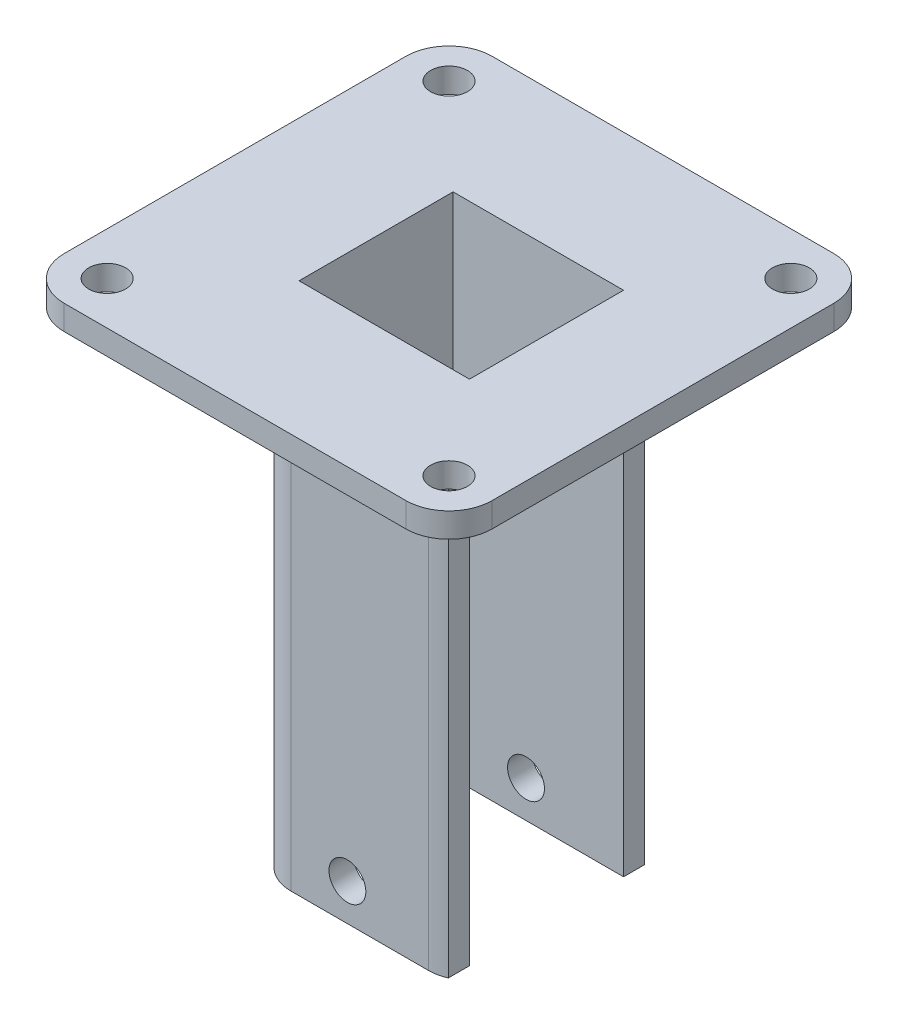
SolidWorks part; units mm, degrees
ref_plane "Front Plane" through (0, 0, 0) normal (0, 0, 1) x (1, 0, 0)
ref_plane "Top Plane" through (0, 0, 0) normal (0, 1, 0) x (1, 0, 0)
ref_plane "Right Plane" through (0, 0, 0) normal (1, 0, 0) x (0, 0, -1)
sketch "Sketch1" plane through (0, 0, 0) normal (0, 1, 0) x (1, 0, 0)
  line L0 (-57.93, -33) -> (48.39, -33)
  line L1 (-57.93, -33) -> (-57.93, 33)
  line L2 (48.39, -33) -> (48.39, 33)
  line L3 (-57.93, 33) -> (48.39, 33)
  line L6 (-6.4, 6.4) -> (6.4, 6.4)
  line L7 (-6.4, 6.4) -> (-6.4, -6.4)
  line L8 (6.4, 6.4) -> (6.4, -6.4)
  line L9 (-6.4, -6.4) -> (6.4, -6.4)
  point P1 (0, 0)
  dimension "D1" = 66
  dimension "D2" = 106.32
  dimension "D3" = 12.8
  dimension "D4" = 6.4
  dimension "D5" = 48.39
  dimension "D6" = 33
  dimension "D7" = 6.4
  dimension "D8" = 12.8
extrude "Boss-Extrude1" add sketch "Sketch1" along normal blind 3
sketch "Sketch2" plane through (0, 3, 0) normal (0, 1, 0) x (1, 0, 0)
  line L0 (-57.93, 33) -> (-57.93, -33) construction
  line L1 (48.39, 33) -> (-57.93, 33) construction
  line L2 (48.39, -33) -> (48.39, 33) construction
  line L3 (-57.93, -33) -> (48.39, -33) construction
  line L4 (-57.93, 33) -> (-57.93, 24)
  line L5 (48.39, 33) -> (39.39, 33)
  line L6 (48.39, -33) -> (48.39, -24)
  line L7 (-57.93, -33) -> (-48.93, -33)
  line L8 (-57.93, 24) -> (-48.93, 24)
  line L9 (-48.93, 24) -> (-48.93, 33)
  line L10 (39.39, 33) -> (39.39, 24)
  line L11 (39.39, 24) -> (48.39, 24)
  line L12 (-57.93, -24) -> (-48.93, -24)
  line L13 (-48.93, -24) -> (-48.93, -33)
  line L14 (-48.93, -33) -> (-48.93, -24)
  line L15 (39.39, -33) -> (39.39, -24)
  line L16 (39.39, -24) -> (48.39, -24)
  line L17 (-57.93, -24) -> (-57.93, -33)
  line L18 (-48.93, 33) -> (-57.93, 33)
  line L19 (39.39, -33) -> (48.39, -33)
  line L20 (48.39, 24) -> (48.39, 33)
  line M1 (-57.93, 33) -> (-57.93, -33)
  line M2 (-57.93, -33) -> (48.39, -33)
  line M3 (48.39, -33) -> (48.39, 33)
  line M4 (48.39, 33) -> (-57.93, 33)
  dimension "D1" = 9
  dimension "D2" = 9
  dimension "D3" = 9
  dimension "D4" = 9
  dimension "D5" = 9
  dimension "D6" = 9
  dimension "D7" = 9
  dimension "D8" = 9
extrude "Boss-Extrude2" [suppressed] add sketch "Sketch2" along normal blind 131 contours L8 L9 M4 M1 | L13 L12 M1 M2 | L16 L15 M2 M3 | L10 L11 M3 M4
sketch "Sketch3" plane through (0, 0, 0) normal (0, -1, 0) x (1, 0, 0)
  line L0 (-8.9, -9.4) -> (11.9, -9.4)
  line L1 (-8.9, -9.4) -> (-8.9, 9.4)
  line L2 (11.9, -9.4) -> (11.9, 9.4)
  line L3 (-8.9, 9.4) -> (11.9, 9.4)
  line L4 (-11.9, 12.4) -> (14.9, 12.4)
  line L5 (14.9, -12.4) -> (14.9, 12.4)
  line L6 (-11.9, -12.4) -> (14.9, -12.4)
  line L7 (-11.9, -12.4) -> (-11.9, 12.4)
  dimension "D1" = 8.9
  dimension "D2" = 20.8
  dimension "D3" = 18.8
  dimension "D4" = 9.4
  dimension "D5" = 3
extrude "Boss-Extrude3" add sketch "Sketch3" along normal blind 62
sketch "Sketch4" plane through (0, 0, -12.4) normal (0, 0, -1) x (-1, 0, 0)
  line L1 (11.9, 0) -> (-14.9, 0) construction
  circle A0 centre (0, -57.5) radius 2.25
  dimension "D1" = 57.5
  dimension "D2" = 4.5
extrude "Cut-Extrude3" cut sketch "Sketch4" against normal through all
fillet "Fillet1" [suppressed] radius 5
fillet "Fillet2" radius 5 4 edges at (-11.9, -31, 12.4) (14.9, -31, -12.4) (14.9, -31, 12.4) (-11.9, -31, -12.4)
sketch "Sketch6" [suppressed] plane through (0, 134, 0) normal (0, 1, 0) x (1, 0, 0)
  line L1 (-57.93, 33) -> (48.39, 33)
  line L2 (-57.93, 33) -> (-57.93, -33)
  line L3 (-57.93, -33) -> (48.39, -33)
  line L4 (48.39, 33) -> (48.39, -33)
extrude "Boss-Extrude4" [suppressed] add sketch "Sketch6" along normal blind 3
sketch "Sketch41" plane through (0, 0, 0) normal (0, -1, 0) x (1, 0, 0)
  line L0 (48.39, 33) -> (48.39, -33) construction
  line L1 (48.39, -33) -> (-57.93, -33) construction
  line L2 (-57.93, -33) -> (-57.93, 33) construction
  line L3 (-57.93, 33) -> (48.39, 33) construction
  line L4 (-6.9, -12.4) -> (9.9, -12.4)
  line L5 (-11.9, 7.4) -> (-11.9, -7.4)
  line L6 (9.9, 12.4) -> (-6.9, 12.4)
  line L7 (14.9, -7.4) -> (14.9, 7.4)
  line L8 (-6.9, -12.4) -> (9.9, -12.4)
  line L9 (-11.9, 7.4) -> (-11.9, -7.4)
  line L10 (9.9, 12.4) -> (-6.9, 12.4)
  line L11 (14.9, -7.4) -> (14.9, 7.4)
  line L12 (-6.9, -12.4) -> (9.9, -12.4) construction
  line L13 (48.39, 33) -> (48.39, -33)
  line L14 (48.39, -33) -> (-57.93, -33)
  line L15 (-57.93, -33) -> (-57.93, 33)
  line L16 (-57.93, 33) -> (48.39, 33)
  line L17 (-6.9, -12.4) -> (9.9, -12.4)
  arc A0 (-11.9, -7.4) -> (-6.9, -12.4) centre (-6.9, -7.4) ccw construction
  arc A1 (-11.9, -7.4) -> (-6.9, -12.4) centre (-6.9, -7.4) ccw
  arc A4 (-11.9, -7.4) -> (-6.9, -12.4) centre (-6.9, -7.4) ccw
  arc A5 (-6.9, 12.4) -> (-11.9, 7.4) centre (-6.9, 7.4) ccw
  arc A6 (14.9, 7.4) -> (9.9, 12.4) centre (9.9, 7.4) ccw
  arc A7 (9.9, -12.4) -> (14.9, -7.4) centre (9.9, -7.4) ccw
  arc A8 (-11.9, -7.4) -> (-6.9, -12.4) centre (-6.9, -7.4) ccw
  arc A9 (-6.9, 12.4) -> (-11.9, 7.4) centre (-6.9, 7.4) ccw
  arc A10 (14.9, 7.4) -> (9.9, 12.4) centre (9.9, 7.4) ccw
  arc A11 (9.9, -12.4) -> (14.9, -7.4) centre (9.9, -7.4) ccw
  line M9 (-57.93, 33) -> (-57.93, -33)
  line M10 (-57.93, -33) -> (48.39, -33)
  line M11 (48.39, -33) -> (48.39, 33)
  line M12 (48.39, 33) -> (-57.93, 33)
  line M13 (9.9, -12.4) -> (-6.9, -12.4)
  arc M14 (-6.9, -12.4) -> (-11.9, -7.4) centre (-6.9, -7.4) cw
  line M15 (-11.9, -7.4) -> (-11.9, 7.4)
  arc M16 (-11.9, 7.4) -> (-6.9, 12.4) centre (-6.9, 7.4) cw
  line M17 (-6.9, 12.4) -> (9.9, 12.4)
  arc M18 (9.9, 12.4) -> (14.9, 7.4) centre (9.9, 7.4) cw
  line M19 (14.9, 7.4) -> (14.9, -7.4)
  arc M20 (14.9, -7.4) -> (9.9, -12.4) centre (9.9, -7.4) cw
  dimension "D1" = 0
extrude "Boss-Extrude16" add sketch "Sketch41" along normal blind 3 contours M12 M9 M10 M11 M20 M13 M14 M15 M16 M17 M18 M19 region at (47.1386, 0, 0)
sketch "Sketch45" plane through (0, 3, 0) normal (0, 1, 0) x (1, 0, 0)
  line L4 (-57.93, 33) -> (-57.93, -33)
  line L5 (-57.93, -33) -> (48.39, -33)
  line L6 (48.39, -33) -> (48.39, 33)
  line L7 (48.39, 33) -> (-57.93, 33)
  line L8 (-57.93, 33) -> (-57.93, -33)
  line L9 (-57.93, -33) -> (48.39, -33)
  line L10 (48.39, -33) -> (48.39, 33)
  line L11 (48.39, 33) -> (-57.93, 33)
  dimension "D1" = 0
extrude "Cut-Extrude22" cut sketch "Sketch45" against normal blind 3
sketch "Sketch46" plane through (0, -3, 0) normal (0, -1, 0) x (1, 0, 0)
  line L0 (11.9, -9.4) -> (11.9, 9.4) construction
  line L1 (14.9, -7.4) -> (14.9, 7.4) construction
  line L2 (-6.9, -12.4) -> (9.9, -12.4) construction
  line L3 (9.9, 12.4) -> (-6.9, 12.4) construction
  line L4 (11.9, -12.4) -> (11.9, 12.4)
  line L5 (14.9, -12.4) -> (14.9, 12.4)
  line L6 (11.9, -12.4) -> (14.9, -12.4)
  line L7 (14.9, 12.4) -> (11.9, 12.4)
extrude "Cut-Extrude23" cut sketch "Sketch46" along normal through all
sketch "Sketch47" plane through (0, -3, 0) normal (0, -1, 0) x (-1, 0, 0)
  line L0 (-27.94, 0) -> (27.94, 0) construction
  line L1 (0, 27.94) -> (0, -27.94) construction
  line L2 (0, 0) -> (-8.6492, 0) construction
  line L3 (0, 0) -> (0, -4.5998) construction
  circle A0 centre (20.86, -20.86) radius 2.25
  circle A1 centre (20.86, 20.86) radius 2.25
  circle A2 centre (-20.86, -20.86) radius 2.25
  circle A3 centre (-20.86, 20.86) radius 2.25
  dimension "D1" = 4.5
  dimension "D2" = 20.86
  dimension "D3" = 20.86
extrude "Cut-Extrude25" cut sketch "Sketch47" against normal through all
sketch "Sketch49" plane through (0, -3, 0) normal (0, -1, 0) x (1, 0, 0)
  line L0 (-20.86, -26.11) -> (20.86, -26.11)
  line L1 (-26.11, -20.86) -> (-26.11, 20.86)
  line L2 (-20.86, 26.11) -> (20.86, 26.11)
  line L3 (26.11, -20.86) -> (26.11, 20.86)
  line L4 (-57.93, -33) -> (48.39, -33) construction
  line L5 (48.39, -33) -> (48.39, 33) construction
  line L6 (48.39, 33) -> (-57.93, 33) construction
  line L7 (-57.93, 33) -> (-57.93, -33) construction
  line L8 (-57.93, -33) -> (48.39, -33)
  line L9 (48.39, -33) -> (48.39, 33)
  line L10 (48.39, 33) -> (-57.93, 33)
  line L11 (-57.93, 33) -> (-57.93, -33)
  circle A24 centre (-20.86, -20.86) radius 5.25
  arc A25 (-26.11, -20.86) -> (-20.86, -26.11) centre (-20.86, -20.86) ccw
  circle A27 centre (20.86, -20.86) radius 5.25
  arc A28 (20.86, -26.11) -> (26.11, -20.86) centre (20.86, -20.86) ccw
  circle A30 centre (-20.86, 20.86) radius 5.25
  arc A31 (-20.86, 26.11) -> (-26.11, 20.86) centre (-20.86, 20.86) ccw
  circle A33 centre (20.86, 20.86) radius 5.25
  arc A34 (26.11, 20.86) -> (20.86, 26.11) centre (20.86, 20.86) ccw
  dimension "D1" = 3
  dimension "D2" = 3
  dimension "D3" = 3
  dimension "D4" = 3
extrude "Cut-Extrude26" cut sketch "Sketch49" against normal through all
fillet "Fillet9" radius 5 9 edges at (10.9215, -3, -12.2945) (1.5, -3, -12.4) (-10.4355, -3, -10.9355) (-11.9, -3, 0) (-10.4355, -3, 10.9355) (10.9215, -3, 12.2945) (11.9, -3, 10.6913) (11.9, -3, -10.6913) (1.5, -3, 12.4)
sketch "Sketch50" plane through (11.9, 0, 0) normal (-1, 0, 0) x (0, 0, 1)
  line L4 (-9.4, -3) -> (9.4, -3)
  line L5 (9.4, -3) -> (9.4, 0)
  line L6 (9.4, 0) -> (-9.4, 0)
  line L7 (-9.4, 0) -> (-9.4, -3)
  line L8 (-9.4, -3) -> (9.4, -3)
  line L9 (9.4, -3) -> (9.4, 0)
  line L10 (9.4, 0) -> (-9.4, 0)
  line L11 (-9.4, 0) -> (-9.4, -3)
  dimension "D1" = 0
extrude "Boss-Extrude17" [suppressed] add sketch "Sketch50" along normal blind 5.5
sketch "Sketch7" [suppressed] plane through (0, 137, 0) normal (0, 1, 0) x (1, 0, 0)
  line L0 (-48.93, -33) -> (39.39, -33) construction
  line L1 (48.39, -33) -> (48.39, 33) construction
  circle A0 centre (0, 0) radius 26.5
  dimension "D1" = 48.39
  dimension "D2" = 53
  dimension "D3" = 33
extrude "Cut-Extrude4" [suppressed] cut sketch "Sketch7" against normal blind 5
sketch "Sketch8" [suppressed] plane through (0, 134, 0) normal (0, -1, 0) x (1, 0, 0)
  line L0 (48.39, -24) -> (45.39, -24)
  line L1 (48.39, -24) -> (48.39, 24)
  line L2 (45.39, -24) -> (45.39, 24)
  line L3 (48.39, 24) -> (45.39, 24)
  line L4 (39.39, 24) -> (48.39, 24) construction
  dimension "D1" = 3
extrude "Boss-Extrude5" [suppressed] add sketch "Sketch8" along normal blind 131
sketch "Sketch10" [suppressed] plane through (0, 134, 0) normal (0, -1, 0) x (1, 0, 0)
  line L4 (0, 0) -> (14.8362, 0) construction
  circle A0 centre (25.3422, 22.8387) radius 1.625
  circle A1 centre (25.3422, -22.8387) radius 1.625
  circle A3 centre (0, 0) radius 26.5 construction
  circle A4 centre (0, 0) radius 26.5
  dimension "D4" = 3.25
  dimension "D5" = 34.115
extrude "Cut-Extrude6" [suppressed] cut sketch "Sketch10" against normal through all contours A0 | A1
sketch "Sketch21" [suppressed] plane through (0, 134, 0) normal (0, -1, 0) x (1, 0, 0)
  circle A0 centre (-33.93, 5.05) radius 1.625
  circle A1 centre (0, 0) radius 26.5 construction
  circle A2 centre (0, 0) radius 26.5
  dimension "D1" = 33.93
  dimension "D3" = 3.25
  dimension "D2" = 5.05
extrude "Cut-Extrude12" [suppressed] cut sketch "Sketch21" against normal up to next contours A0
sketch "Sketch11" [suppressed] plane through (0, 134, 0) normal (0, -1, 0) x (1, 0, 0)
  line L0 (-66, 44) -> (-47.7966, 14.3367) construction
  line L1 (-37.8467, 24.3295) -> (-35.4201, 26.404)
  line L2 (-45.5, 30) -> (-48.93, 47)
  line L5 (-45.5, 33) -> (-48.93, 33)
  line L8 (-48.93, 24) -> (-48.93, 33) construction
  line L9 (-48.93, 47) -> (-48.93, 33)
  line L11 (-45.7507, 11.0029) -> (-47.7966, 14.3367)
  line L12 (-51.4178, 12.7275) -> (-48.9912, 14.802)
  arc A3 (-37.8467, 24.3295) -> (-45.5, 30) centre (-45.5, 22) ccw
  arc A6 (-35.4201, 26.404) -> (-45.5, 33) centre (-45.5, 22) ccw
  arc A7 (-47.7966, 14.3367) -> (-48.9912, 14.802) centre (-45.5, 22) ccw
  circle A8 centre (-45.5, 22) radius 11 construction
  circle A9 centre (-45.5, 22) radius 8 construction
  arc A10 (-45.7507, 11.0029) -> (-51.4178, 12.7275) centre (-45.5, 22) ccw
  point P3 (-45.5, 22)
  point P4 (-23.505, 28.7245)
  point P5 (-23.505, 28.7245)
  point P8 (-27, 50)
  point P11 (-27, 45)
  point P16 (-17.5, 22)
  point P25 (-17.5, 22)
  dimension "D1" = 3
extrude "Boss-Extrude6" [suppressed] add sketch "Sketch11" along normal blind 12.2
sketch "Sketch12" [suppressed] plane through (0, 121.8, 0) normal (0, -1, 0) x (1, 0, 0)
  line L0 (-36.5645, -4.536) -> (-34.8232, -0.6054) construction
  line L1 (-45.5, 50) -> (-60, 50) construction
  line L2 (-36.5645, -4.536) -> (-19.842, 33.2102)
  line L3 (-45.5, 50) -> (-60, 50)
  line L5 (-60, 50) -> (-60, 47) construction
  line L6 (-60, 50) -> (-60, 44)
  line L7 (-66, 44) -> (-60, 44) construction
  line L8 (-47.3545, -2.9311) -> (-46.1381, -5.9927) construction
  line L10 (-66, 44) -> (-60, 44)
  line L11 (-66, 44) -> (-46.1381, -5.9927)
  arc A0 (-46.1381, -5.9927) -> (-36.5645, -4.536) centre (-45.5, 22) ccw construction
  arc A1 (-19.842, 33.2102) -> (-45.5, 50) centre (-45.5, 22) ccw construction
  arc A2 (-46.1381, -5.9927) -> (-36.5645, -4.536) centre (-45.5, 22) ccw
  arc A3 (-19.842, 33.2102) -> (-45.5, 50) centre (-45.5, 22) ccw
  point P9 (-56, 25.1613)
  point P12 (-61, 50)
  point P13 (-61, 25.1613)
  point P15 (-61, 35)
  point P16 (-56, 35)
extrude "Boss-Extrude7" [suppressed] add sketch "Sketch12" along normal blind 5
sketch "Sketch13" [suppressed] plane through (0, 116.8, 0) normal (0, -1, 0) x (1, 0, 0)
  line L2 (-66, 44) -> (-46.1381, -5.9927) construction
  line L3 (-59.8699, 28.5705) -> (-53.0906, 11.5068)
  arc A2 (-53.0906, 11.5068) -> (-59.8699, 28.5705) centre (-49.8906, 22.6567) ccw
  dimension "D1" = 23.2
extrude "Cut-Extrude7" [suppressed] cut sketch "Sketch13" against normal blind 2
sketch "Sketch14" [suppressed] plane through (0, 116.8, 0) normal (0, -1, 0) x (1, 0, 0)
  line L0 (-62.8216, 36) -> (-31.5, 36)
  line L1 (-45.5, 50) -> (-60, 50) construction
  line L2 (-66, 44) -> (-59.8699, 28.5705) construction
  line L3 (-66, 44) -> (-62.8216, 36)
  line L4 (-59.8164, 36) -> (-31.5, 36) construction
  line L5 (-60.7854, 39) -> (-62.7719, 44)
  line L6 (-31.5, 8) -> (-31.5, 36)
  line L7 (-66, -44) -> (-66, 44) construction
  line L8 (-36.5645, -4.536) -> (-19.842, 33.2102) construction
  line L9 (-53.0906, 11.5068) -> (-46.1381, -5.9927) construction
  line L10 (-28.5, 13.6674) -> (-28.5, 39)
  line L11 (-60.7854, 39) -> (-28.5, 39)
  line L12 (-59.8164, 39) -> (-28.5, 39) construction
  line L13 (-28.5, 6.8958) -> (-28.5, 39) construction
  line L14 (-31.5, 8) -> (-51.6974, 8)
  line L15 (-51.6974, 8) -> (-50.5055, 5)
  line L17 (-32.3399, 5) -> (-28.5, 13.6674)
  line L18 (-31.0108, 8) -> (-50.9566, 8) construction
  line L19 (-32.3399, 5) -> (-50.5055, 5)
  line L20 (-31.5, 6.8958) -> (-28.5, 13.6674)
  line L21 (-31.0108, 5) -> (-50.9566, 5) construction
  line L22 (-31.5, 6.8958) -> (-31.5, 36) construction
  line L23 (-60, 44) -> (-66, 44) construction
  line L24 (-62.7719, 44) -> (-66, 44)
  point P16 (-59, 42)
  point P17 (-56, 40)
  dimension "D1" = 14
  dimension "D2" = 34.5
  dimension "D3" = 3
  dimension "D4" = 42
  dimension "D6" = 3
  dimension "D5" = 3
extrude "Boss-Extrude8" [suppressed] add sketch "Sketch14" along normal blind 24
sketch "Sketch29" [suppressed] plane through (0, 134, 0) normal (0, -1, 0) x (1, 0, 0)
  line L1 (-57.93, -24) -> (-57.93, 24) construction
  line L4 (-48.93, 24) -> (-48.93, 27)
  line L5 (-48.93, 24) -> (-48.93, 33) construction
  line L6 (-57.93, 2) -> (-41.93, 2)
  line L7 (-57.93, 5) -> (-41.93, 5)
  line L8 (-48.93, 24) -> (-41.93, 24)
  line L9 (-48.93, 27) -> (-41.93, 27)
  line L14 (-57.93, 2) -> (-57.93, 5)
  arc A0 (-41.93, 2) -> (-41.93, 27) centre (-41.93, 14.5) ccw
  arc A1 (-41.93, 5) -> (-41.93, 24) centre (-41.93, 14.5) ccw
  circle A3 centre (-41.93, 14.5) radius 12.5 construction
  circle A4 centre (-41.93, 14.5) radius 9.5 construction
  point P1 (-32.2829, 11.5)
  point P15 (-29.8291, 15.1546)
  dimension "D1" = 25
  dimension "D3" = 3
  dimension "D4" = 16
extrude "Boss-Extrude12" [suppressed] add sketch "Sketch29" along normal blind 11.3 contours L14 L7 A1 L8 L4 L9 A0 L6
sketch "Sketch25" [suppressed] plane through (0, 122.7, 0) normal (0, -1, 0) x (1, 0, 0)
  line L2 (-57.93, 24) -> (-41.93, 24) construction
  line L3 (-57.93, 5) -> (-57.93, 24) construction
  line L4 (-57.93, 5) -> (-57.93, 24)
  line L6 (-57.93, 5) -> (-41.93, 5) construction
  line L7 (-57.93, 24) -> (-41.93, 24)
  line L8 (-57.93, 5) -> (-41.93, 5)
  arc A0 (-41.93, 5) -> (-41.93, 24) centre (-41.93, 14.5) ccw construction
  arc A1 (-41.93, 5) -> (-41.93, 24) centre (-41.93, 14.5) ccw
  circle A2 centre (-41.93, 14.5) radius 3.9
  point P13 (-42.4424, 11.9931)
  point P14 (-32.8261, 23.4534)
  point P15 (-48.4176, 17.0069)
  point P16 (-38.8013, 28.4671)
  dimension "D1" = 7.8
extrude "Boss-Extrude11" [suppressed] add sketch "Sketch25" against normal blind 3
sketch "Sketch32" [suppressed] plane through (0, 137, 0) normal (0, 1, 0) x (1, 0, 0)
  line L6 (-42.2096, -2.5625) -> (-42.2096, 0.578) construction
  line L7 (-48.5223, 1) -> (-45.43, 1) construction
  line L8 (-48.5223, -2) -> (-48.5223, 1) construction
  line L9 (-42.2096, -20.4375) -> (-42.2096, -23.578) construction
  line L10 (-48.5223, -24) -> (-45.43, -24) construction
  line L11 (-48.5223, -21) -> (-48.5223, -24) construction
  line L13 (-42.2096, -2.5625) -> (-42.2096, 0.578)
  line L14 (-48.5223, 1) -> (-45.43, 1)
  line L15 (-48.5223, -2) -> (-48.5223, 1)
  line L16 (-42.2096, -20.4375) -> (-42.2096, -23.578)
  line L17 (-48.5223, -24) -> (-45.43, -24)
  line L18 (-48.5223, -21) -> (-48.5223, -24)
  arc A2 (-42.2096, 0.578) -> (-45.43, 1) centre (-45.43, -11.5) ccw construction
  arc A3 (-45.43, -24) -> (-42.2096, -23.578) centre (-45.43, -11.5) ccw construction
  arc A6 (-42.2096, 0.578) -> (-45.43, 1) centre (-45.43, -11.5) ccw
  arc A7 (-45.43, -24) -> (-42.2096, -23.578) centre (-45.43, -11.5) ccw
  arc A8 (-48.5223, -21) -> (-42.2096, -20.4375) centre (-45.43, -20) ccw
  arc A9 (-42.2096, -2.5625) -> (-48.5223, -2) centre (-45.43, -3) ccw
  dimension "D1" = 6.5
sketch "Sketch37" [suppressed] plane through (0, 125.7, 0) normal (0, 1, 0) x (1, 0, 0)
  line L0 (-57.93, -5) -> (-57.93, -24) construction
  line L1 (-41.93, -5) -> (-57.93, -5) construction
  line L2 (-57.93, -24) -> (-41.93, -24) construction
  line L3 (-57.93, -5) -> (-57.93, -24)
  line L4 (-41.93, -5) -> (-57.93, -5)
  line L5 (-57.93, -24) -> (-41.93, -24)
  line L6 (-32.9925, -17.7204) -> (-29.852, -17.7204)
  line L7 (-32.9925, -11.2796) -> (-29.852, -11.2796)
  arc A0 (-41.93, -24) -> (-41.93, -5) centre (-41.93, -14.5) ccw construction
  arc A1 (-41.93, -24) -> (-32.9925, -17.7204) centre (-41.93, -14.5) ccw
  arc A5 (-32.9925, -11.2796) -> (-41.93, -5) centre (-41.93, -14.5) ccw
  arc A6 (-29.852, -17.7204) -> (-29.852, -11.2796) centre (-41.93, -14.5) ccw
  dimension "D3" = 25
extrude "Cut-Extrude20" [suppressed] cut sketch "Sketch37" along normal up to surface (11.3 mm away) contours A5 L4 L3 L5 A1 L6 A6 L7
sketch "Sketch38" [suppressed] plane through (0, 125.7, 0) normal (0, 1, 0) x (1, 0, 0)
  circle A0 centre (-33.43, -14.3622) radius 1.9875
  circle A1 centre (-50.43, -14.3622) radius 1.9875
  circle A2 centre (-41.93, -14.5) radius 3.9 construction
  dimension "D1" = 3.975
  dimension "D2" = 3.975
  dimension "D3" = 17
  dimension "D4" = 8.5
extrude "Cut-Extrude21" [suppressed] cut sketch "Sketch38" against normal up to surface (3 mm away)
extrude "Boss-Extrude13" [suppressed] add sketch "Sketch32" against normal up to surface (3 mm away)
sketch "Sketch36" [suppressed] plane through (0, 134, 0) normal (0, -1, 0) x (1, 0, 0)
  circle A10 centre (-33.93, 5.05) radius 8
  circle A11 centre (-33.93, 5.05) radius 8
  dimension "D3" = 6.375
extrude "Cut-Extrude19" [suppressed] cut sketch "Sketch36" along normal up to surface (8.3 mm away) contours A11
fillet "Fillet3" [suppressed] radius 2
fillet "Fillet4" [suppressed] radius 5
chamfer "Chamfer1" [suppressed] distance 4 angle 45
fillet "Fillet5" [suppressed] radius 0.8
sketch "Sketch16" [suppressed] plane through (0, 134, 0) normal (0, -1, 0) x (1, 0, 0)
  line L2 (-57.93, -24) -> (-57.93, 2) construction
  line L4 (-48.93, 33) -> (39.39, 33) construction
  line L5 (39.39, -33) -> (-48.93, -33) construction
  circle A0 centre (-23.67, -26) radius 1.6
  circle A1 centre (16.33, -26) radius 1.6
  circle A4 centre (16.33, 26) radius 1.6
  circle A5 centre (-23.67, 26) radius 1.6
  dimension "D4" = 3.2
  dimension "D2" = 7
  dimension "D1" = 7
  dimension "D3" = 40
  dimension "D5" = 34.26
extrude "Cut-Extrude13" [suppressed] cut sketch "Sketch16" against normal blind 10
sketch "Sketch22" [suppressed] plane through (0, 137, 0) normal (0, 1, 0) x (1, 0, 0)
  line L0 (0, 0) -> (18.4844, 0) construction
  line L1 (48.39, -28.6686) -> (48.39, 28.6686) construction
  line L2 (-57.93, 28.6686) -> (-57.93, -5) construction
  circle A0 centre (40.555, 0) radius 2.375
  circle A1 centre (-50.095, 0) radius 2.375
  dimension "D1" = 4.75
  dimension "D4" = 4.75
  dimension "D2" = 7.835
  dimension "D3" = 7.835
extrude "Cut-Extrude14" [suppressed] cut sketch "Sketch22" against normal up to surface (11.3 mm away)
sketch "Sketch34" [suppressed] plane through (0, 134, 0) normal (0, -1, 0) x (1, 0, 0)
  line L0 (-45.3294, -4.7656) -> (-45.3294, 7.2344)
  line L1 (-54.8606, 7.2344) -> (-54.8606, -4.7656)
  line L2 (-50.095, -11.5275) -> (-50.095, -0.8064) construction
  line L3 (-50.095, 0) -> (-48.5122, 0) construction
  line L4 (-54.8606, 7.2344) -> (-45.3294, 7.2344)
  line L5 (-45.3294, -4.7656) -> (-54.8606, -4.7656)
  arc A0 (-51.3759, 2) -> (-48.8141, 2) centre (-50.095, 0) ccw construction
  dimension "D5" = 4.7656
  dimension "D1" = 9.5312
  dimension "D2" = 4.7656
  dimension "D3" = 0
  dimension "D4" = 12
extrude "Cut-Extrude18" [suppressed] cut sketch "Sketch34" along normal up to surface (8.3 mm away)
sketch "Sketch17" [suppressed] plane through (0, 134, 0) normal (0, -1, 0) x (1, 0, 0)
  line L0 (48.39, 28.6686) -> (48.39, -28.6686) construction
  line L1 (42.39, 11) -> (38.39, 11)
  line L2 (42.39, 11) -> (42.39, -11)
  line L3 (42.39, -11) -> (38.39, -11)
  line L4 (38.39, 11) -> (38.39, -11)
  circle A0 centre (0, 0) radius 26.5 construction
  dimension "D1" = 22
  dimension "D2" = 4
  dimension "D3" = 11
  dimension "D4" = 10
extrude "Cut-Extrude9" [suppressed] cut sketch "Sketch17" against normal up to next
sketch "Sketch18" [suppressed] plane through (0, 134, 0) normal (0, -1, 0) x (1, 0, 0)
  line L0 (-57.93, -24) -> (-57.93, 2) construction
  line L1 (-49.93, -5.5) -> (-54.93, -5.5)
  line L2 (-49.93, -5.5) -> (-49.93, -11)
  line L3 (-49.93, -11) -> (-54.93, -11)
  line L4 (-54.93, -5.5) -> (-54.93, -11)
  circle A0 centre (0, 0) radius 26.5 construction
  dimension "D1" = 5.5
  dimension "D2" = 5
  dimension "D3" = 11
  dimension "D4" = 3
extrude "Cut-Extrude10" [suppressed] cut sketch "Sketch18" against normal up to next
sketch "Sketch19" [suppressed] plane through (0, 137, 0) normal (0, 1, 0) x (1, 0, 0)
  line L0 (44.0586, 33) -> (-53.5986, 33) construction
  line L1 (-24.15, 33) -> (-18, 33)
  line L2 (-24.15, 33) -> (-24.15, 26.85)
  line L3 (-24.15, 26.85) -> (-18, 26.85)
  line L4 (-18, 33) -> (-18, 26.85)
  line L5 (-53.5986, -33) -> (44.0586, -33) construction
  line L6 (18, 33) -> (24.15, 33)
  line L7 (18, 33) -> (18, 26.85)
  line L8 (18, 26.85) -> (24.15, 26.85)
  line L9 (24.15, 33) -> (24.15, 26.85)
  line L10 (-24.15, -33) -> (-18, -33)
  line L11 (-24.15, -33) -> (-24.15, -26.85)
  line L12 (-24.15, -26.85) -> (-18, -26.85)
  line L13 (-18, -33) -> (-18, -26.85)
  line L14 (-57.93, 28.6686) -> (-57.93, -5) construction
  line L15 (18, -33) -> (24.15, -33)
  line L16 (18, -33) -> (18, -26.85)
  line L17 (18, -26.85) -> (24.15, -26.85)
  line L18 (24.15, -33) -> (24.15, -26.85)
  circle A0 centre (0, 0) radius 26.5 construction
  dimension "D1" = 6.15
  dimension "D2" = 36
  dimension "D3" = 18
  dimension "D4" = 33.78
extrude "Cut-Extrude11" [suppressed] cut sketch "Sketch19" against normal up to next
sketch "Sketch33" [suppressed] plane through (0, 122.7, 0) normal (0, -1, 0) x (-1, 0, 0)
  circle A0 centre (45.43, -11.5) radius 12.5
sketch "Sketch39" [suppressed] plane through (0, 134, 0) normal (0, -1, 0) x (1, 0, 0)
  line L0 (-48.93, 33) -> (39.39, 33) construction
  line L1 (-48.93, 27) -> (-48.93, 33) construction
  line L2 (-48.93, 27) -> (-41.93, 27) construction
  line L3 (-48.93, 33) -> (-23.93, 33)
  line L4 (-48.93, 27) -> (-48.93, 33)
  line L5 (-48.93, 27) -> (-23.93, 27)
  line L6 (-23.93, 27) -> (-23.93, 33)
  dimension "D1" = 25
extrude "Boss-Extrude14" [suppressed] add sketch "Sketch39" along normal blind 35
sketch "Sketch40" [suppressed] plane through (0, 134, 0) normal (0, -1, 0) x (1, 0, 0)
  line L0 (-41.93, 27) -> (-23.93, 27) construction
  line L1 (-41.93, 27) -> (-29.852, 27)
  line L2 (-29.852, 17.7204) -> (-29.852, 27)
  arc A0 (-29.852, 17.7204) -> (-41.93, 27) centre (-41.93, 14.5) ccw construction
  arc A1 (-29.852, 17.7204) -> (-41.93, 27) centre (-41.93, 14.5) ccw
extrude "Boss-Extrude15" [suppressed] add sketch "Sketch40" along normal up to surface (11.3 mm away)
fillet "Fillet6" [suppressed] radius 0.8
fillet "Fillet7" [suppressed] radius 0.8
fillet "Fillet8" [suppressed] radius 0.8
